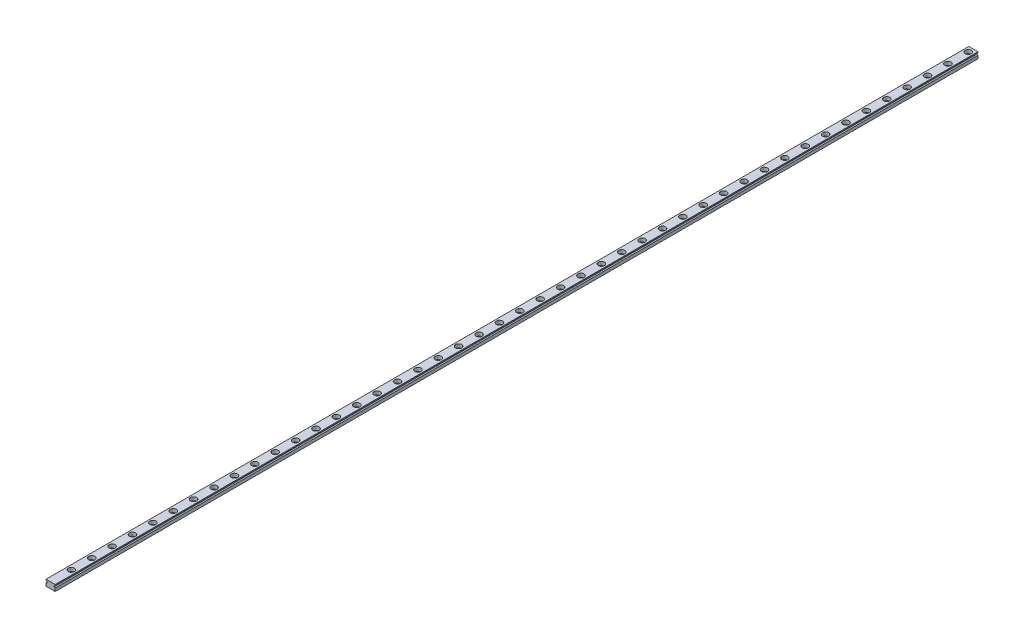
SolidWorks part; units mm, degrees
ref_plane "Front Plane" through (0, 0, 0) normal (0, 0, 1) x (1, 0, 0)
ref_plane "Top Plane" through (0, 0, 0) normal (0, 1, 0) x (1, 0, 0)
ref_plane "Right Plane" through (0, 0, 0) normal (1, 0, 0) x (0, 0, -1)
sketch "Sketch1" plane through (0, 0, 0) normal (0, 0, 1) x (1, 0, 0)
  line L0 (0, 0) -> (0, 5.7299) construction
  line L1 (-4.5, -3) -> (4.5, -3)
  line L2 (-4.5, -3) -> (-4.5, 0)
  line L3 (-4.5, 3) -> (4.5, 3)
  line L4 (4.5, -3) -> (4.5, 0)
  line L5 (-4.5, -3) -> (4.5, 3) construction
  line L6 (-4.5, 3) -> (4.5, -3) construction
  line L7 (-4.5, 2) -> (-4.5, 3)
  line L8 (-3.564, 0.648) -> (-3.2351, 0.648)
  line L9 (3.564, 0.648) -> (3.2351, 0.648)
  line L10 (-3.564, 1.352) -> (-3.2351, 1.352)
  line L11 (-3.2351, 0.648) -> (-3.2351, 1.352)
  line L12 (3.2351, 0.648) -> (3.2351, 1.352)
  line L13 (3.564, 1.352) -> (3.2351, 1.352)
  line L14 (4.5, 2) -> (4.5, 3)
  arc A0 (-3.564, 1.352) -> (-4.5, 2) centre (-4.5, 1) ccw
  arc A1 (-4.5, 0) -> (-3.564, 0.648) centre (-4.5, 1) ccw
  arc A2 (4.5, 0) -> (3.564, 0.648) centre (4.5, 1) cw
  arc A3 (3.564, 1.352) -> (4.5, 2) centre (4.5, 1) cw
  point P0 (0, 0)
  dimension "D3" = 1
  dimension "D1" = 9
  dimension "D2" = 6
  dimension "D4" = 2
extrude "Extrude1" add sketch "Sketch1" along normal blind 905.4
sketch "Sketch2" plane through (0, 3, 0) normal (0, 1, 0) x (1, 0, 0)
  line L0 (4.5, 0) -> (-4.5, 0) construction
  circle A0 centre (0, -5) radius 1.75
  circle A1 centre (0, -5) radius 3
  dimension "D1" = 3.5
  dimension "D2" = 6
  dimension "D3" = 5
extrude "Extrude2" cut sketch "Sketch2" against normal blind 3.5 contours A1
extrude "Extrude3" cut sketch "Sketch" against normal through all contours A0
sketch "Sketch" plane through (0, 3, 0) normal (0, 1, 0) x (1, 0, 0) same geometry as "Sketch2"
pattern_linear "LPattern1" count 45 spacing 20 along (0, 0, 1) of "Extrude2", "Extrude3"
